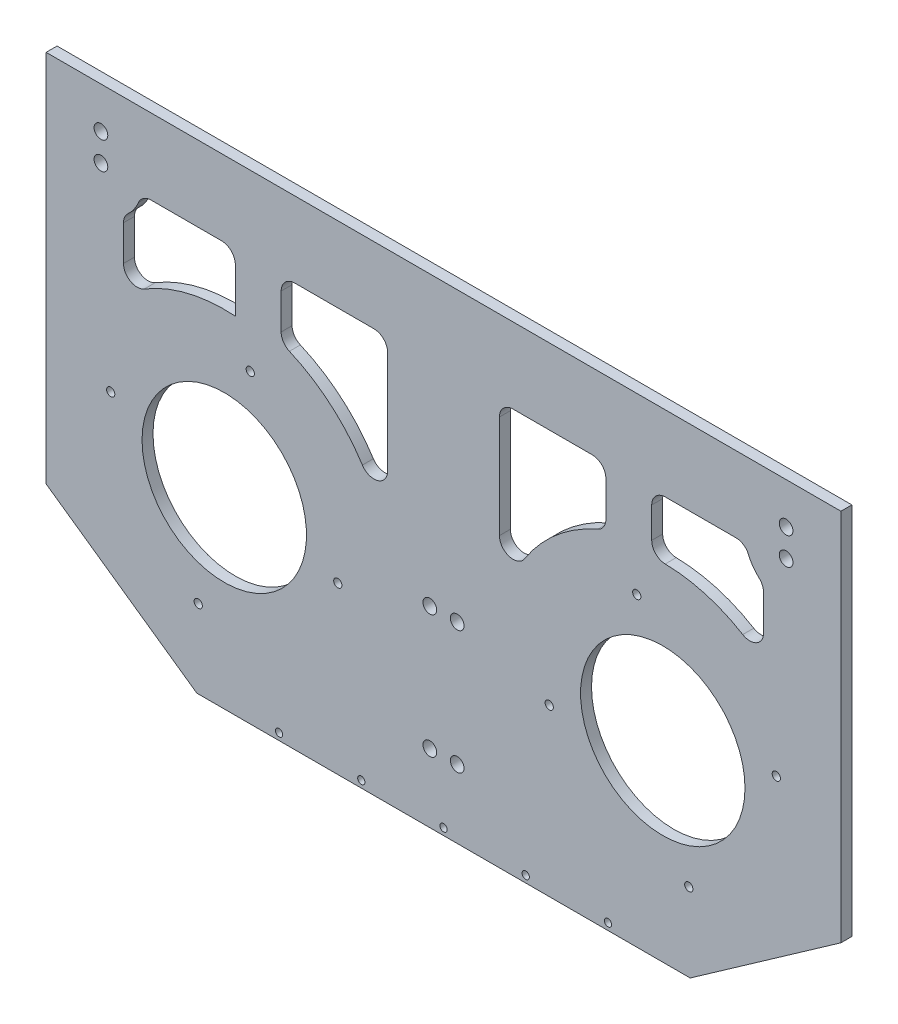
SolidWorks part; units mm, degrees
ref_plane "Front Plane" through (0, 0, 0) normal (0, 0, 1) x (1, 0, 0)
ref_plane "Top Plane" through (0, 0, 0) normal (0, 1, 0) x (1, 0, 0)
ref_plane "Right Plane" through (0, 0, 0) normal (1, 0, 0) x (0, 0, -1)
sketch "Sketch1" plane through (0, 0, 0) normal (0, 0, 1) x (1, 0, 0)
  line L0 (-125, 100) -> (125, 100) construction
  line L1 (-125, 0) -> (125, 0) construction
  line L2 (-145, -16.3871) -> (-90, -55)
  line L3 (-90, -55) -> (90, -55)
  line L4 (90, -55) -> (145, -16.3871)
  line L5 (-125, 105) -> (-125, 95) construction
  line L6 (0, -55) -> (0, 100) construction
  line L7 (-145, 120) -> (145, 120)
  line L8 (145, 120) -> (145, -16.3871)
  line L11 (-145, -16.3871) -> (-145, 120)
  line L12 (125, 105) -> (125, 95) construction
  line L13 (-5, -30) -> (5, -30) construction
  circle A0 centre (-125, 100) radius 12.5 construction
  circle A10 centre (-125, 0) radius 12.5 construction
  circle A11 centre (125, 0) radius 12.5 construction
  circle A12 centre (-125, 0) radius 17.5 construction
  circle A13 centre (-125, 100) radius 17.5 construction
  circle A25 centre (-125, 95) radius 2.5
  circle A26 centre (-125, 105) radius 2.5
  circle A27 centre (125, 95) radius 2.5
  circle A28 centre (125, 105) radius 2.5
  circle A29 centre (5, -30) radius 2.5
  circle A30 centre (-5, -30) radius 2.5
  point P12 (0, 100)
  point P15 (0, -30)
  point P45 (0, 120)
  dimension "D1" = 25
  dimension "D2" = 5
  dimension "D4" = 100
  dimension "D6" = 5
  dimension "D11" = 20
  dimension "D12" = 20
  dimension "D7" = 10
  dimension "D8" = 250
  dimension "D3" = 25
  dimension "D5" = 30
  dimension "D9" = 180
extrude "Boss-Extrude1" add sketch "Sketch1" along normal blind 4
sketch "Sketch2" plane through (0, 0, 4) normal (0, 0, 1) x (1, 0, 0)
  line L0 (121.4264, 24.4924) -> (38.5736, 5.5076) construction
  line L1 (89.4924, -26.4264) -> (70.5076, 56.4264) construction
  line L2 (0, 0) -> (0, 96.4486) construction
  line L3 (145, 120) -> (-145, 120) construction
  line L4 (-145, 120) -> (-145, -16.3871) construction
  line L5 (-80, 15) -> (80, 15) construction
  line L6 (-5, 15) -> (5, 15) construction
  circle A0 centre (80, 15) radius 42.5 construction
  circle A1 centre (38.5736, 5.5076) radius 1.5
  circle A2 centre (70.5076, 56.4264) radius 1.5
  circle A3 centre (121.4264, 24.4924) radius 1.5
  circle A4 centre (89.4924, -26.4264) radius 1.5
  circle A5 centre (80, 15) radius 30
  circle A6 centre (-38.5736, 5.5076) radius 1.5
  circle A7 centre (-70.5076, 56.4264) radius 1.5
  circle A8 centre (-89.4924, -26.4264) radius 1.5
  circle A9 centre (-121.4264, 24.4924) radius 1.5
  circle A10 centre (-80, 15) radius 42.5 construction
  circle A11 centre (-80, 15) radius 30
  circle A12 centre (-80, 15) radius 47.5 construction
  circle A15 centre (-5, 15) radius 2.5
  circle A16 centre (5, 15) radius 2.5
  point P6 (80, 15)
  point P27 (-80, 15)
  point P30 (0, 15)
  dimension "D1" = 85
  dimension "D2" = 3
  dimension "D3" = 60
  dimension "D4" = 95
  dimension "D5" = 5
  dimension "D6" = 105
  dimension "D7" = 65
  dimension "D8" = 10
extrude "Cut-Extrude1" cut sketch "Sketch2" against normal blind 10
sketch "Sketch3" plane through (0, 0, 4) normal (0, 0, 1) x (1, 0, 0)
  line L0 (-90, -55) -> (90, -55) construction
  circle A0 centre (0, -52.5) radius 1.325
  circle A1 centre (30, -52.5) radius 1.325
  circle A2 centre (60, -52.5) radius 1.325
  circle A3 centre (-30, -52.5) radius 1.325
  circle A4 centre (-60, -52.5) radius 1.325
  point P0 (0, -52.5)
  dimension "D2" = 2.65
  dimension "D1" = 2.5
  dimension "D4" = 30
  dimension "D6" = 30
extrude "Cut-Extrude2" cut sketch "Sketch3" against normal up to surface (4 mm away) up to face at (-122.9264, 24.4924, 0)
sketch "Sketch6" plane through (0, 0, 0) normal (0, 0, -1) x (-1, 0, 0)
  line L0 (-20.3921, 20.3957) -> (-20.3921, 92.4562)
  line L1 (-20.3921, 92.4562) -> (-59.2398, 92.4562)
  line L2 (-59.2398, 92.4562) -> (-59.2398, 71.1358)
  line L3 (-75.9623, 92.4562) -> (-110.4197, 92.4562)
  line L4 (-75.9623, 92.4562) -> (-75.9623, 71.1358)
  line L5 (-116.7764, 82.6944) -> (-116.7764, 57.603)
  line L6 (0, -55) -> (0, 120) construction
  line L7 (90, -55) -> (-90, -55) construction
  line L8 (-145, 120) -> (145, 120) construction
  line L9 (20.3921, 20.3957) -> (20.3921, 92.4562)
  line L10 (20.3921, 92.4562) -> (59.2398, 92.4562)
  line L11 (59.2398, 92.4562) -> (59.2398, 71.1358)
  line L12 (75.9623, 92.4562) -> (75.9623, 71.1358)
  line L13 (75.9623, 92.4562) -> (110.4197, 92.4562)
  line L14 (116.7764, 82.6944) -> (116.7764, 57.603)
  arc A0 (-20.3921, 20.3957) -> (-59.2398, 71.1358) centre (-80, 15) ccw
  arc A1 (-75.9623, 71.1358) -> (-116.7764, 57.603) centre (-80, 15) ccw
  arc A2 (-110.4197, 92.4562) -> (-116.7764, 82.6944) centre (-125, 95) cw
  arc A3 (20.3921, 20.3957) -> (59.2398, 71.1358) centre (80, 15) cw
  arc A4 (75.9623, 71.1358) -> (116.7764, 57.603) centre (80, 15) cw
  arc A5 (110.4197, 92.4562) -> (116.7764, 82.6944) centre (125, 95) ccw
extrude "Cut-Extrude3" cut sketch "Sketch6" along direction (0, 0, -1) on the side against the normal up to surface (4 mm away) contours L3 A2 L5 A1 L4 | A0 L0 L1 L2 | L9 A3 L11 L10 | A5 L13 L12 A4 L14 region at (36.1386, 72.1325, 0) region at (97.4759, 79.2288, 0) region at (-36.1386, 72.1325, 0) region at (-97.4759, 79.2288, 0) up to face at (-58.675, -52.5, 4)
fillet "Fillet1" radius 5 17 edges at (-59.2398, 92.4562, 2) (-110.4197, 92.4562, 2) (-116.7764, 82.6944, 2) (-59.2398, 71.1358, 2) (-116.7764, 57.603, 2) (-75.9623, 92.4562, 2) (-20.3921, 92.4562, 2) (-20.3921, 20.3957, 2) (20.3921, 20.3957, 2) (59.2398, 92.4562, 2) (59.2398, 71.1358, 2) (20.3921, 92.4562, 2) (75.9623, 92.4562, 2) (75.9623, 71.1358, 2) (110.4197, 92.4562, 2) (116.7764, 82.6944, 2) (116.7764, 57.603, 2)
equation "\"D1@Sketch1\" = \"cf_tube_outer_diameter\""
equation "\"mid_plate_mid_to_top\" = 100mm"
equation "\"mid_plate_mid_to_bottom\" = 30mm"
equation "\"mid_plate_horizontal_spacing\"=250mm"
equation "\"cf_tube_outer_diameter\"= 25mm"
equation "\"D4@Sketch1\"=\"mid_plate_mid_to_top\""
equation "\"cf_tube_inner_diameter\" = 21mm"
equation "\"mid_tube_length\" = 500mm"
equation "\"cf_plate_thickness\" =4mm"
equation "\"D1@Boss-Extrude1\"=\"cf_plate_thickness\""
equation "\"D8@Sketch1\"=\"mid_plate_horizontal_spacing\""
equation "\"D5@Sketch1\"=\"mid_plate_mid_to_bottom\""
equation "\"mid_plate_bottom_width\" = 180mm"
equation "\"D9@Sketch1\"=\"mid_plate_bottom_width\""
equation "\"mid_support_plate_distance\" = 250mm"
equation "\"nut_strip_2_hole_distance\" = 7mm"
equation "\"nut_strip_hole_diameter\" = 2.5mm"
equation "\"nut_strip_hole_to_edge_distance\"= 2.5mm"
equation "\"D1@Sketch3\"=\"nut_strip_hole_to_edge_distance\""
equation "\"D2@Sketch3\"=\"nut_strip_hole_diameter\"+0.15mm"
